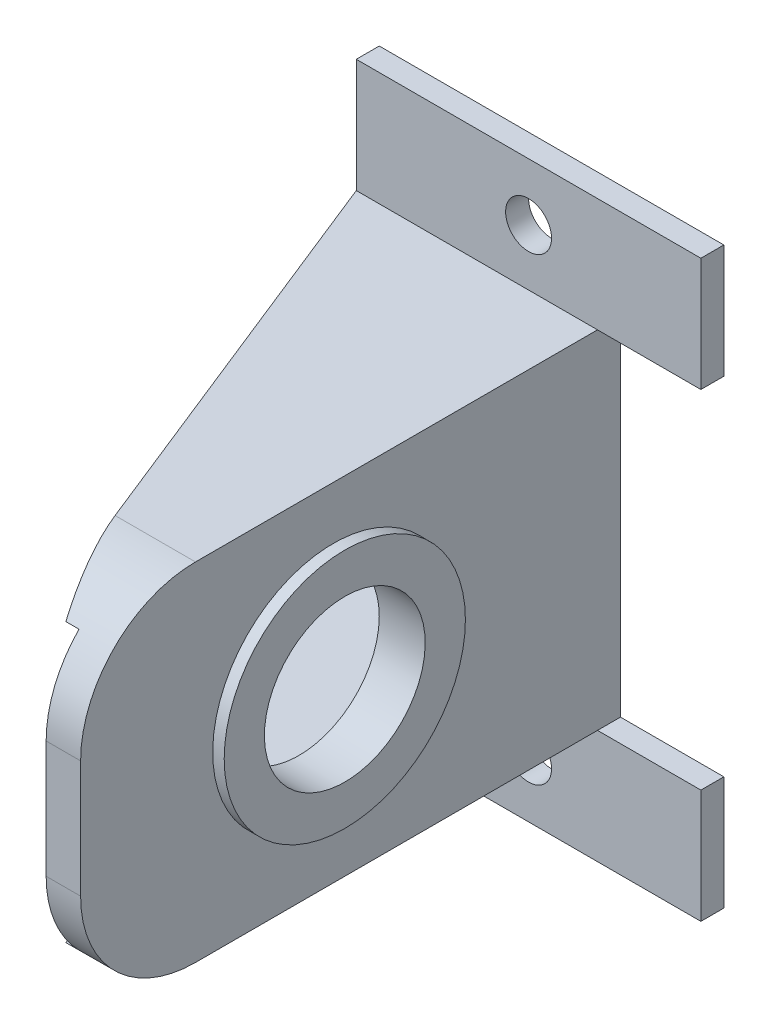
SolidWorks part; units mm, degrees
material "ABS"
ref_plane "Plan de face" through (0, 0, 0) normal (0, 0, 1) x (1, 0, 0)
ref_plane "Plan de dessus" through (0, 0, 0) normal (0, 1, 0) x (1, 0, 0)
ref_plane "Plan de droite" through (0, 0, 0) normal (1, 0, 0) x (0, 0, -1)
sketch "Esquisse1" plane through (0, 0, 0) normal (0, 0, 1) x (1, 0, 0)
  line L0 (30, 40.1) -> (21, 40.1)
  line L1 (0, 0) -> (30, 0)
  line L2 (0, 0) -> (0, 50)
  line L3 (0, 50) -> (30, 50)
  line L4 (30, 50) -> (30, 40.1)
  line L5 (21, 40.1) -> (21, 9.9)
  line L6 (21, 9.9) -> (30, 9.9)
  line L7 (30, 9.9) -> (30, 0)
  line L8 (30, 50) -> (15, 50) construction
  line L9 (15, 50) -> (15, 0) construction
  circle A0 centre (15, 45) radius 2
  circle A1 centre (15, 5) radius 2
  dimension "D7" = 4
  dimension "D8" = 4
  dimension "D1" = 50
  dimension "D2" = 30
  dimension "D3" = 30.2
  dimension "D4" = 9.9
  dimension "D5" = 9
  dimension "D6" = 15
  dimension "D9" = 5
  dimension "D10" = 5
extrude "Boss.-Extru.1" add sketch "Esquisse1" along normal blind 2
sketch "Esquisse2" plane through (0, 0, 2) normal (0, 0, 1) x (1, 0, 0)
  line L0 (18, 40.1) -> (0, 40.1)
  line L1 (21, 40.1) -> (18, 40.1)
  line L2 (21, 40.1) -> (21, 9.9)
  line L3 (21, 9.9) -> (18, 9.9)
  line L5 (0, 50) -> (0, 0) construction
  line L6 (0, 40.1) -> (0, 37.1)
  line L7 (0, 37.1) -> (18, 37.1)
  line L8 (18, 37.1) -> (18, 12.9)
  line L9 (18, 12.9) -> (0, 12.9)
  line L10 (0, 12.9) -> (0, 9.9)
  line L11 (0, 9.9) -> (18, 9.9)
  dimension "D1" = 30.2
  dimension "D2" = 3
  dimension "D3" = 3
  dimension "D4" = 3
extrude "Boss.-Extru.2" add sketch "Esquisse2" along normal blind 45
sketch "Esquisse3" plane through (0, 9.9, 0) normal (0, -1, 0) x (1, 0, 0)
  line L0 (0, 2) -> (18, 47)
  line L1 (0, 47) -> (21, 47) construction
  line L2 (18, 47) -> (0, 47)
  line L3 (0, 47) -> (0, 2)
  dimension "D1" = 3
extrude "Enlèv. mat.-Extru.2" cut sketch "Esquisse3" against normal up to surface (30.2 mm away) up to face at (10.5, 40.1, 24.5)
sketch "Esquisse4" plane through (21, 0, 0) normal (1, 0, 0) x (0, 0, -1)
  line L0 (0, 9.9) -> (0, 40.1) construction
  line L1 (-47, 40.1) -> (-2, 40.1) construction
  circle A0 centre (-25, 25) radius 10.5
  dimension "D1" = 21
  dimension "D2" = 25
  dimension "D3" = 15.1
extrude "Boss.-Extru.3" add sketch "Esquisse4" along normal blind 1
sketch "Esquisse5" plane through (22, 0, 0) normal (1, 0, 0) x (0, 0, -1)
  circle A0 centre (-25, 25) radius 7
  circle A1 centre (-25, 25) radius 10.5 construction
  dimension "D1" = 14
  dimension "D2" = 0
  dimension "D3" = 15.1
extrude "Enlèv. mat.-Extru.3" cut sketch "Esquisse5" against normal up to next
fillet "Congé1" radius 10 2 edges at (19.5, 40.1, 47) (19.5, 9.9, 47)
